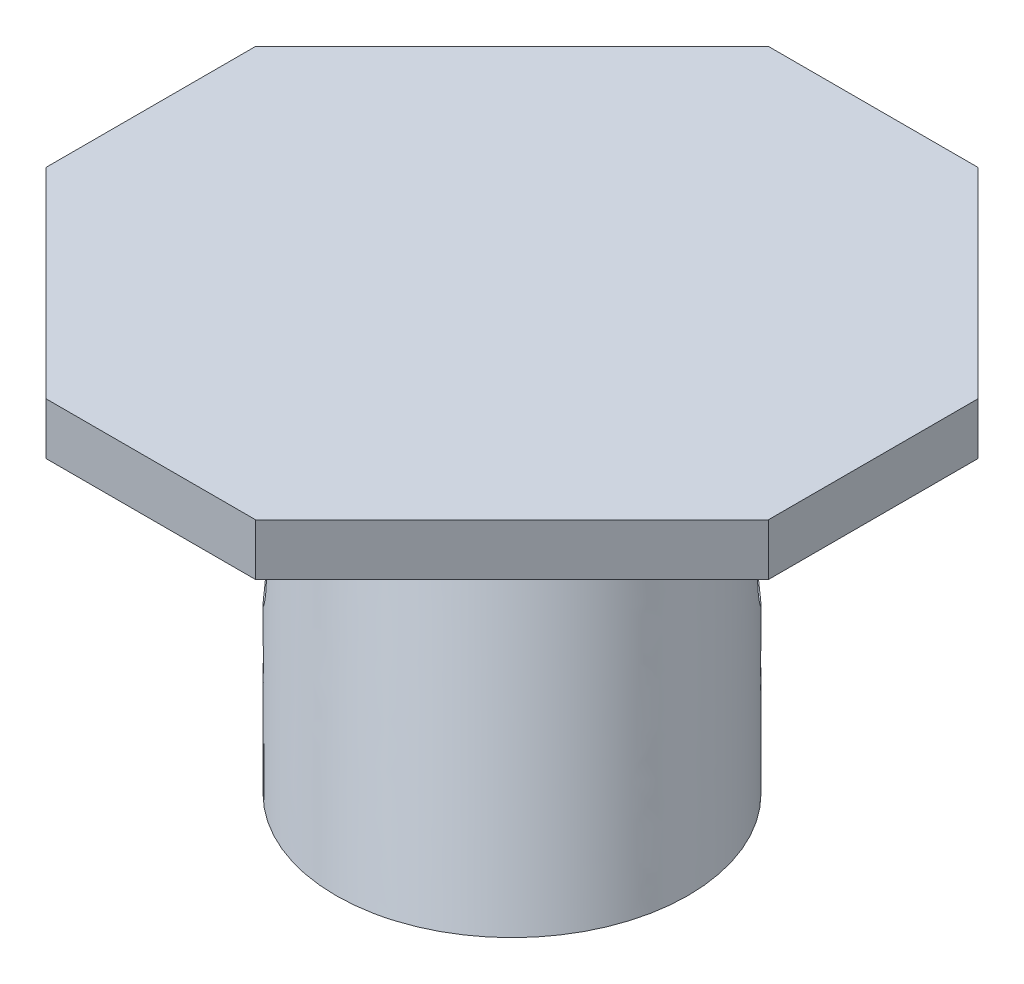
SolidWorks part; units mm, degrees
ref_plane "Front Plane" through (0, 0, 0) normal (0, 0, 1) x (1, 0, 0)
ref_plane "Top Plane" through (0, 0, 0) normal (0, 1, 0) x (1, 0, 0)
ref_plane "Right Plane" through (0, 0, 0) normal (1, 0, 0) x (0, 0, -1)
sketch "Sketch1" plane through (0, 0, 0) normal (0, 1, 0) x (1, 0, 0)
  line L0 (-40.3039, 15.5552) -> (-15.5552, 40.3039)
  line L1 (-40.3039, -40.3039) -> (40.3039, -40.3039) construction
  line L2 (-40.3039, -40.3039) -> (-40.3039, 40.3039) construction
  line L3 (-40.3039, 40.3039) -> (40.3039, 40.3039) construction
  line L4 (40.3039, -40.3039) -> (40.3039, 40.3039) construction
  line L5 (-40.3039, -40.3039) -> (40.3039, 40.3039) construction
  line L6 (-40.3039, 40.3039) -> (40.3039, -40.3039) construction
  line L7 (-27.9296, 27.9296) -> (2.476, -2.476) construction
  line L8 (-11.6661, -16.6182) -> (16.6182, 11.6661) construction
  line L9 (-11.6661, -16.6182) -> (-32.8793, 4.5951) construction
  line L10 (16.6182, 11.6661) -> (-4.5951, 32.8793) construction
  line L11 (-40.3039, 15.5552) -> (-40.3039, -4.6948)
  line L12 (-15.5552, 40.3039) -> (4.6948, 40.3039)
  line L13 (24.0428, 0.706) -> (24.0428, 20.956)
  line L14 (-0.706, -24.0428) -> (-20.956, -24.0428)
  line L15 (-32.8793, 4.5951) -> (-4.5951, 32.8793) construction
  line L16 (-18.7372, 18.7372) -> (11.6684, -11.6684) construction
  line L17 (-0.706, -24.0428) -> (24.0428, 0.706)
  line L18 (-40.3039, -4.6948) -> (-20.956, -24.0428)
  line L19 (4.6948, 40.3039) -> (24.0428, 20.956)
  point P0 (0, 0)
  point P13 (2.476, -2.476)
  point P28 (11.6684, -11.6684)
  dimension "D1" = 135
  dimension "D2" = 35
  dimension "D3" = 43
  dimension "D4" = 40
  dimension "D5" = 30
  dimension "D7" = 20.25
  dimension "D8" = 20.25
  dimension "D9" = 43
  dimension "D10" = 35
  dimension "D11" = 20.25
  dimension "D12" = 20.25
extrude "Boss-Extrude1" add sketch "Sketch1" along normal blind 5
sketch "Sketch3" plane through (0, 0, 0) normal (0, -1, 0) x (1, 0, 0)
  line L0 (-30.63, 14.3688) -> (14.3688, -30.63) construction
  line L1 (-40.3039, 4.6948) -> (-20.956, 24.0428) construction
  line L2 (24.0428, -20.956) -> (4.6948, -40.3039) construction
  line L3 (-8.1306, -8.1306) -> (11.6684, 11.6684) construction
  line L4 (-0.706, 24.0428) -> (24.0428, -0.706) construction
  circle A0 centre (-8.1306, -8.1306) radius 14
  circle A1 centre (-8.1306, -8.1306) radius 17
  dimension "D1" = 28
  dimension "D2" = 3
ref_plane "Plane1" through (0, -25, 0) normal (0, -1, 0) x (-1, 0, 0)
ref_plane "Plane2" through (0, 0, 0) normal (0.7071, 0, -0.7071) x (-0.7071, 0, -0.7071)
sketch "Sketch5" plane through (0, -25, 0) normal (0, -1, 0) x (-1, 0, 0)
  line L0 (8.1306, 8.1306) -> (-11.6684, -11.6684) construction
  point P7 (8.1306, 8.1306)
sketch "Sketch6" plane through (0, 0, 0) normal (0.7071, 0, -0.7071) x (-0.7071, 0, -0.7071)
  line L0 (-5.5016, 0) -> (28.4984, 0) construction
  line L2 (11.4984, 0) -> (-16.5016, 0) construction
  line L3 (11.4984, 0) -> (0.5793, -30)
  point P0 (11.4984, 0)
  dimension "D1" = 70
  dimension "D2" = 30
sweep "Sweep2" add profiles "Sketch3" path "Sketch6"
sketch "Sketch8" plane through (0, 0, 0) normal (0.7071, 0, -0.7071) x (-0.7071, 0, -0.7071)
  line L0 (11.4984, 0) -> (0.5793, -30) construction
  circle A0 centre (6.0388, -15) radius 2.6
  dimension "D1" = 5.2
extrude "Cut-Extrude2" cut sketch "Sketch8" against normal blind 20 and the other way blind 20
fillet "Fillet2" radius 3 1 edges at (-8.1306, 0, -25.1306)
